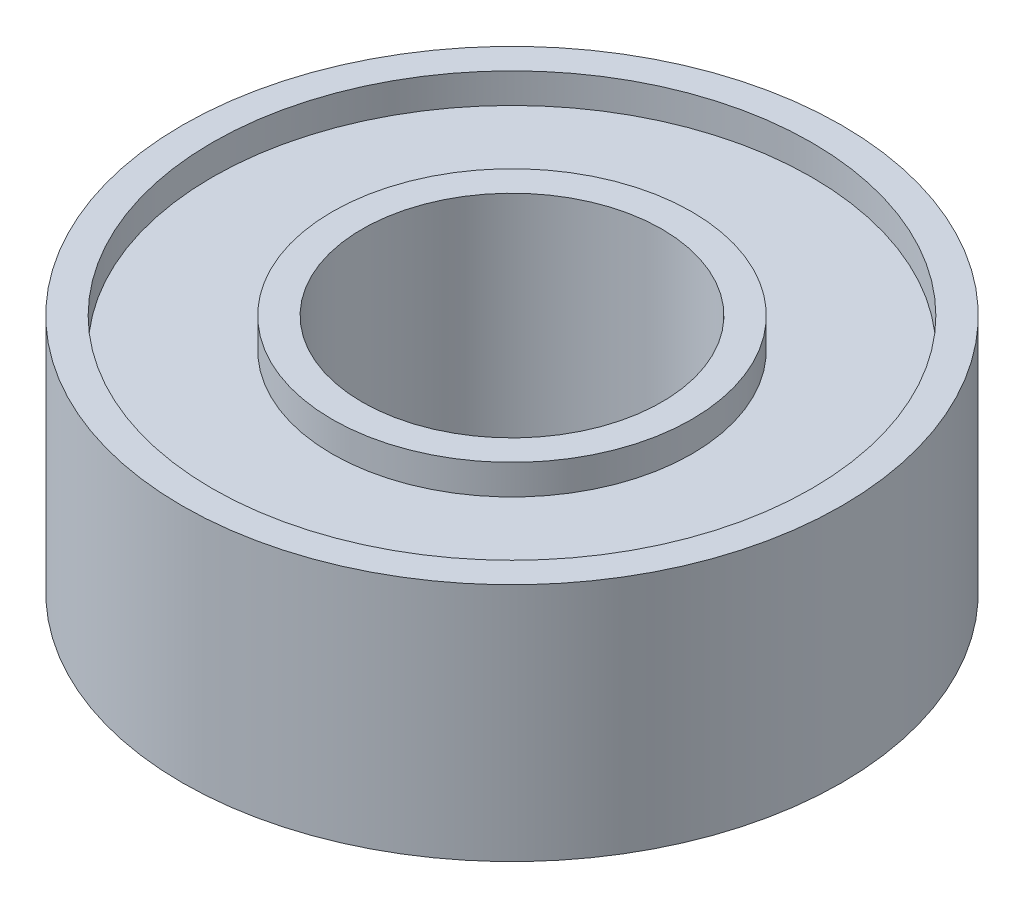
SolidWorks part; units mm, degrees
material "AISI 304"
ref_plane "Front Plane" through (0, 0, 0) normal (0, 0, 1) x (1, 0, 0)
ref_plane "Top Plane" through (0, 0, 0) normal (0, 1, 0) x (1, 0, 0)
ref_plane "Right Plane" through (0, 0, 0) normal (1, 0, 0) x (0, 0, -1)
sketch "Sketch1" plane through (0, 0, 0) normal (0, 1, 0) x (1, 0, 0)
  circle A0 centre (0, 0) radius 5.5
  circle A1 centre (0, 0) radius 2.5
  dimension "D1" = 11
  dimension "D2" = 5
extrude "Boss-Extrude1" add sketch "Sketch1" along normal blind 4
sketch "Sketch2" plane through (0, 4, 0) normal (0, 1, 0) x (1, 0, 0)
  circle A0 centre (0, 0) radius 5
  circle A2 centre (0, 0) radius 5.5 construction
  circle A3 centre (0, 0) radius 3
  circle A4 centre (0, 0) radius 2.5 construction
  dimension "D1" = 0.5
  dimension "D2" = 0.5
extrude "Cut-Extrude1" cut sketch "Sketch2" against normal blind 0.5
extrude "Cut-Extrude2" cut sketch "Sketch2<2>" along normal blind 0.5 from surface starting at face at (0, 0, 5.5)
sketch "Sketch2<2>" plane through (0, 4, 0) normal (0, 1, 0) x (1, 0, 0) same geometry as "Sketch2"
